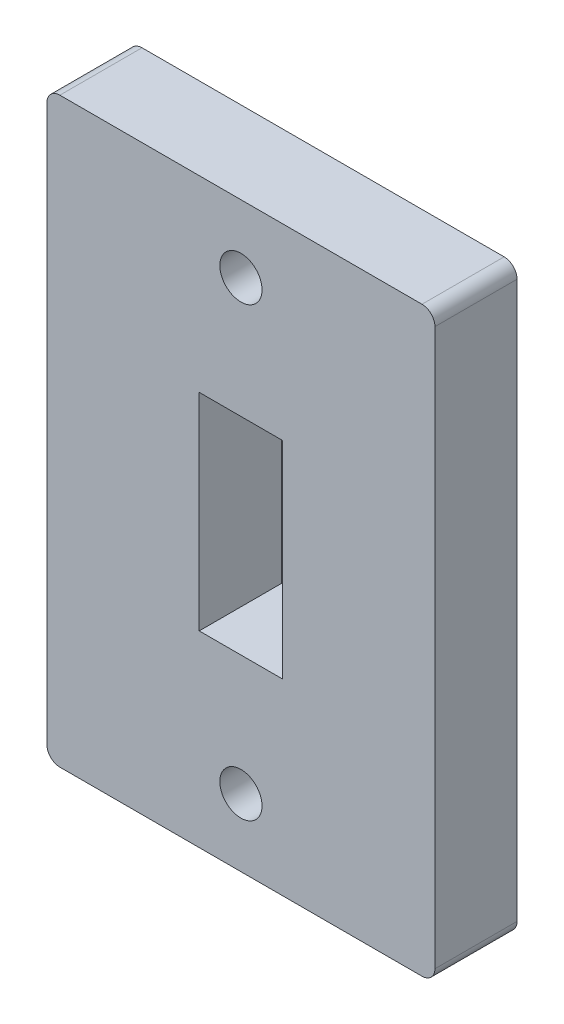
SolidWorks part; units mm, degrees
ref_plane "Front Plane" through (0, 0, 0) normal (0, 0, 1) x (1, 0, 0)
ref_plane "Top Plane" through (0, 0, 0) normal (0, 1, 0) x (1, 0, 0)
ref_plane "Right Plane" through (0, 0, 0) normal (1, 0, 0) x (0, 0, -1)
sketch "Sketch1" plane through (0, 0, 0) normal (0, 0, 1) x (1, 0, 0)
  line L0 (60, -45) -> (0, -45) construction
  line L1 (0, 0) -> (60, 0)
  line L2 (0, 0) -> (0, -90)
  line L3 (0, -90) -> (60, -90)
  line L4 (60, 0) -> (60, -90)
  line L5 (30, -45) -> (30, -29.025) construction
  line L6 (30, -29.025) -> (36.45, -29.025)
  line L7 (36.45, -29.025) -> (36.45, -60.975)
  line L8 (36.45, -60.975) -> (30, -60.975)
  line L9 (30, -60.975) -> (23.55, -60.975)
  line L10 (23.55, -60.975) -> (23.55, -29.025)
  line L11 (23.55, -29.025) -> (30, -29.025)
  line L12 (30, -45) -> (30, -60.975) construction
  line L13 (30, 0) -> (30, -13.25) construction
  line L14 (30, -90) -> (30, -79.56) construction
  dimension "D1" = 90
  dimension "D2" = 60
  dimension "D3" = 12.9
  dimension "D4" = 31.95
  dimension "D5" = 13.25
  dimension "D6" = 10.44
extrude "Boss-Extrude1" add sketch "Sketch1" along normal blind 12.7
sketch "Sketch4" plane through (0, 0, 0) normal (0, 0, -1) x (-1, 0, 0)
  line L0 (-30, 0) -> (-30, -10.44)
  line L1 (-60, 0) -> (0, 0) construction
  line L2 (-30, -90) -> (-30, -79.56)
  line L3 (0, -90) -> (-60, -90) construction
  line L4 (-30, -79.56) -> (-30, -10.44) construction
  dimension "D3" = 69.12
hole_wizard "CSK for 1/4 Flat Head Machine Screw1" positions "Sketch5" profile "Sketch6" countersink size "1/4" standard "ANSI Inch" end condition through all
sketch "Sketch5" plane through (0, 0, 0) normal (0, 0, -1) x (-1, 0, 0)
  point P0 (-30, -10.44)
  point P3 (-30, -79.56)
sketch "Sketch6" plane through (30, -10.44, 0) normal (1, 0, 0) x (0, 1, 0)
  line L0 (0, 0) -> (0, 12.7)
  line L1 (0, 12.7) -> (3.2639, 12.7)
  line L2 (3.2639, 12.7) -> (3.2639, 3.6524)
  line L3 (3.2639, 3.6524) -> (6.4389, 0)
  line L5 (6.4389, 0) -> (0, 0)
  line L6 (-3.2639, 3.6524) -> (-6.4389, 0) construction
  line L11 (0, -6.35) -> (0, 107.95) construction
  dimension "Thru Hole Dia." = 6.5278
  dimension "Thru Hole Depth" = 12.7
  dimension "Near C'Sink Dia." = 12.8778
  dimension "Near C'Sink Angle" = 82
fillet "Fillet1" radius 2 4 edges at (0, 0, 6.35) (60, 0, 6.35) (0, -90, 6.35) (60, -90, 6.35)
